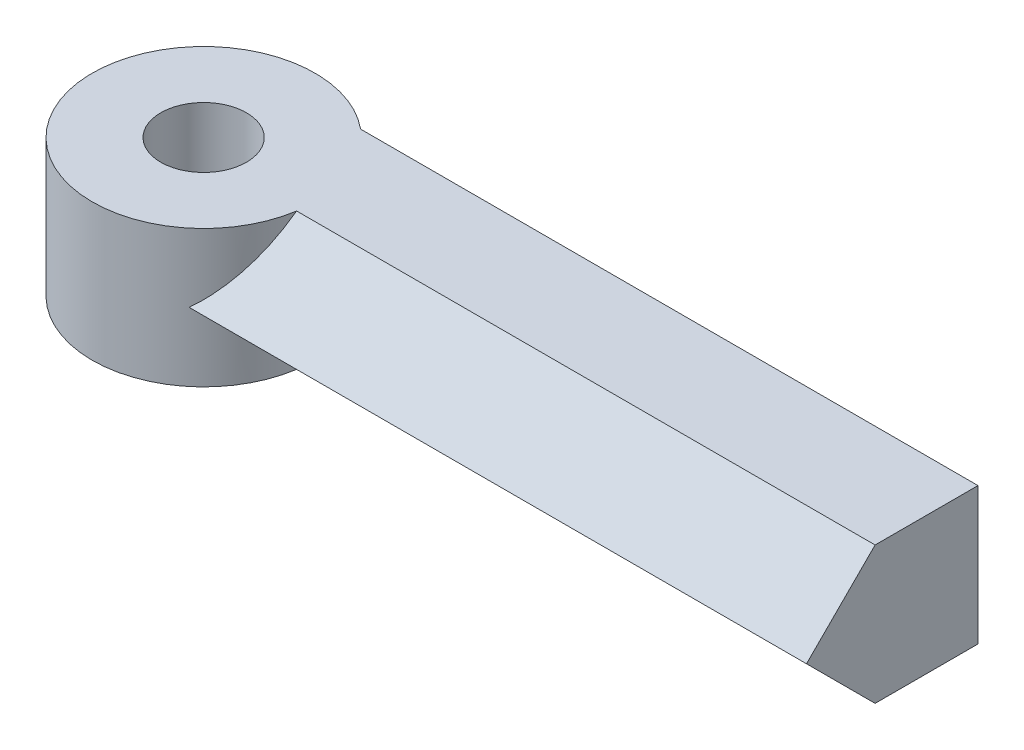
SolidWorks part; units mm, degrees
ref_plane "Alzado" through (0, 0, 0) normal (0, 0, 1) x (1, 0, 0)
ref_plane "Planta" through (0, 0, 0) normal (0, 1, 0) x (1, 0, 0)
ref_plane "Vista lateral" through (0, 0, 0) normal (1, 0, 0) x (0, 0, -1)
sketch "Croquis1" plane through (0, 0, 0) normal (0, 1, 0) x (1, 0, 0)
  circle A0 centre (0, 0) radius 1.25
  circle A1 centre (0, 0) radius 3.25
  dimension "D1" = 2.5
  dimension "D2" = 2
extrude "Saliente-Extruir1" add sketch "Croquis1" along normal blind 4
sketch "Croquis2" plane through (0, 4, 0) normal (0, 1, 0) x (1, 0, 0)
  line L0 (2.0767, 2.5) -> (2.0767, -2.5)
  line L1 (2.0767, 2.5) -> (20.0767, 2.5)
  line L2 (20.0767, 2.5) -> (20.0767, -2.5)
  line L3 (20.0767, -2.5) -> (2.0767, -2.5)
  circle A0 centre (0, 0) radius 3.25 construction
  dimension "D1" = 18
  dimension "D2" = 5
extrude "Saliente-Extruir2" add sketch "Croquis2" against normal blind 4
chamfer "Chaflán1" distance 2 angle 45 2 edges at (11.0767, 0, 2.5) (11.0767, 4, 2.5)
